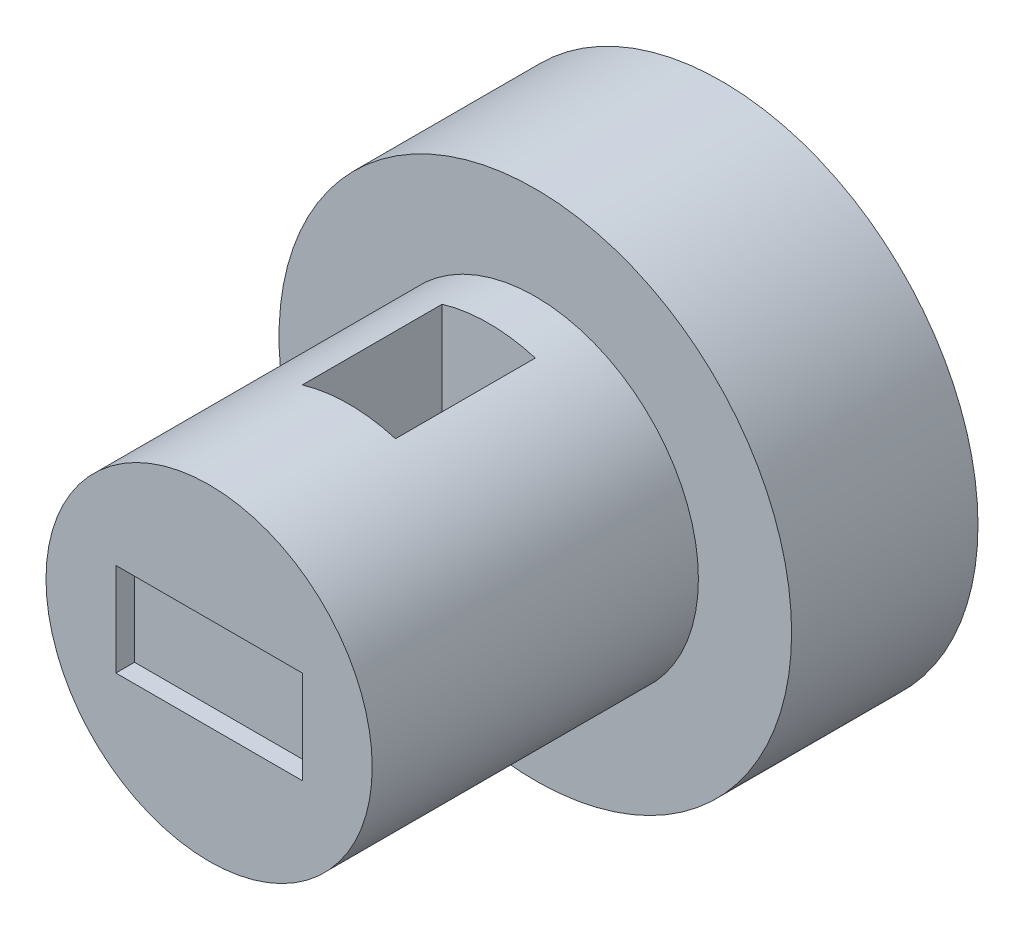
SolidWorks part; units mm, degrees
ref_plane "Спереди" through (0, 0, 0) normal (0, 0, 1) x (1, 0, 0)
ref_plane "Сверху" through (0, 0, 0) normal (0, 1, 0) x (1, 0, 0)
ref_plane "Справа" through (0, 0, 0) normal (1, 0, 0) x (0, 0, -1)
sketch "Эскиз1" plane through (0, 0, 0) normal (0, 0, 1) x (1, 0, 0)
  circle A0 centre (0, 0) radius 27.5
  dimension "D1" = 55
extrude "Бобышка-Вытянуть1" add sketch "Эскиз1" along normal blind 20
sketch "Эскиз2" plane through (0, 0, 0) normal (0, 0, 1) x (1, 0, 0)
  circle A0 centre (0, 0) radius 20
  dimension "D1" = 40
extrude "Вырез-Вытянуть1" cut sketch "Эскиз2" along normal blind 15
sketch "Эскиз3" plane through (0, 0, 0) normal (0, 0, 1) x (1, 0, 0)
  circle A0 centre (0, 0) radius 17.5
  dimension "D1" = 35
extrude "Бобышка-Вытянуть2" add sketch "Эскиз3" along normal blind 35 from offset 20
sketch "Эскиз4" plane through (0, 0, 0) normal (0, 1, 0) x (1, 0, 0)
  line L1 (-5, -25) -> (5, -25)
  line L2 (-5, -25) -> (-5, -40)
  line L3 (-5, -40) -> (5, -40)
  line L4 (5, -25) -> (5, -40)
  point P4 (0, -25)
  dimension "D1" = 10
  dimension "D2" = 15
  dimension "D3" = 25
extrude "Вырез-Вытянуть2" cut sketch "Эскиз4" against normal blind 40 from offset 20
sketch "Эскиз5" plane through (0, 0, 55) normal (0, 0, 1) x (1, 0, 0)
  line L1 (-10, -5) -> (10, -5)
  line L2 (-10, -5) -> (-10, 5)
  line L3 (-10, 5) -> (10, 5)
  line L4 (10, -5) -> (10, 5)
  line L5 (-10, -5) -> (10, 5) construction
  line L6 (-10, 5) -> (10, -5) construction
  point P0 (0, 0)
  point P5 (0, 0)
  point P6 (0, 0)
  dimension "D1" = 10
  dimension "D2" = 20
extrude "Вырез-Вытянуть3" cut sketch "Эскиз5" against normal blind 2
